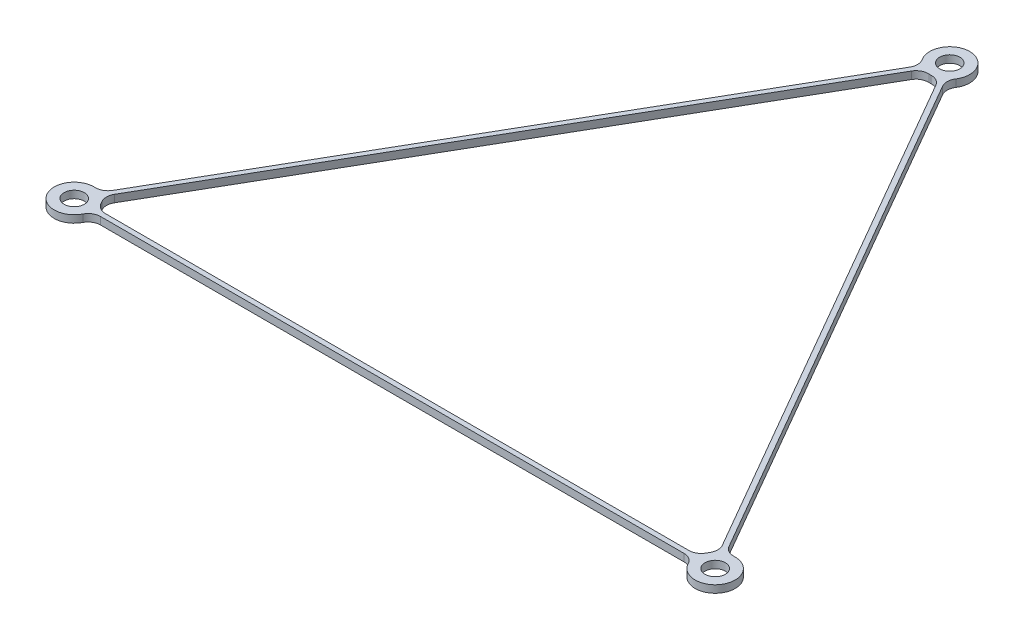
SolidWorks part; units mm, degrees
other "Markup1"
sketch "Sketch1" plane through (0, 0, 0) normal (0.4, 0.515, 0.7581) x (0.8844, 0, -0.4667)
ref_plane "Front Plane" through (0, 0, 0) normal (0, 0, 1) x (1, 0, 0)
ref_plane "Top Plane" through (0, 0, 0) normal (0, 1, 0) x (1, 0, 0)
ref_plane "Right Plane" through (0, 0, 0) normal (1, 0, 0) x (0, 0, -1)
sketch "Sketch2" plane through (0, 0, 0) normal (0, 1, 0) x (1, 0, 0)
  line L0 (65, -37.5278) -> (0, 0) construction
  line L1 (0, 0) -> (0, 75.0555) construction
  line L2 (0, 0) -> (-65, -37.5278) construction
  line L3 (65, -37.5278) -> (-65, -37.5278) construction
  line L4 (-65, -37.5278) -> (0, 75.0555) construction
  line L5 (0, 75.0555) -> (65, -37.5278) construction
  line L6 (-63.4235, -33.7972) -> (-2.4425, 71.825)
  line L7 (63.4235, -33.7972) -> (2.4425, 71.825)
  line L8 (60.981, -38.0278) -> (-60.981, -38.0278)
  line L9 (-60.981, -37.0278) -> (60.981, -37.0278)
  line L10 (62.5575, -34.2972) -> (1.5765, 71.325)
  line L11 (-1.5765, 71.325) -> (-62.5575, -34.2972)
  line L12 (-32.933, 19.0139) -> (-32.067, 18.5139) construction
  line L13 (0, -38.0278) -> (0, -37.0278) construction
  line L14 (32.933, 19.0139) -> (32.067, 18.5139) construction
  circle A0 centre (0, 75.0555) radius 2.05
  circle A1 centre (65, -37.5278) radius 2.05
  circle A2 centre (-65, -37.5278) radius 2.05
  arc A3 (62.5575, -34.2972) -> (60.981, -37.0278) centre (65, -37.5278) ccw
  arc A4 (-60.981, -37.0278) -> (-62.5575, -34.2972) centre (-65, -37.5278) ccw
  arc A5 (2.4425, 71.825) -> (-2.4425, 71.825) centre (0, 75.0555) ccw
  arc A6 (60.981, -38.0278) -> (63.4235, -33.7972) centre (65, -37.5278) ccw
  arc A7 (-63.4235, -33.7972) -> (-60.981, -38.0278) centre (-65, -37.5278) ccw
  arc A8 (-1.5765, 71.325) -> (1.5765, 71.325) centre (0, 75.0555) ccw
  point P14 (32.5, 18.7639)
  point P21 (-32.5, 18.7639)
  point P23 (0, -37.5278)
  dimension "D2" = 4.1
  dimension "D3" = 2
  dimension "D1" = 130
  dimension "D4" = 1
extrude "main_shape" add sketch "Sketch2" along normal mid plane 1.5
fillet "outside_fillet" radius 2.5 6 edges at (-2.4425, 0, -71.825) (2.4425, 0, -71.825) (63.4235, 0, 33.7972) (60.981, 0, 38.0278) (-60.981, 0, 38.0278) (-63.4235, 0, 33.7972)
fillet "inside_fillet" radius 2.5 6 edges at (-62.5575, 0, 34.2972) (-60.981, 0, 37.0278) (60.981, 0, 37.0278) (62.5575, 0, 34.2972) (1.5765, 0, -71.325) (-1.5765, 0, -71.325)
